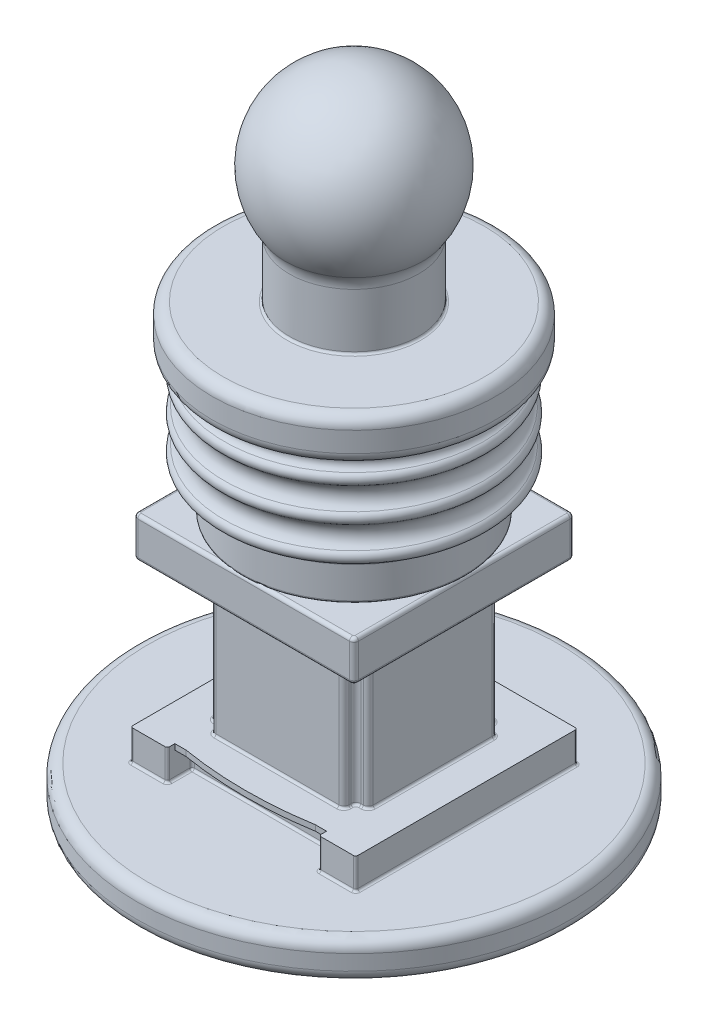
SolidWorks part; units mm, degrees
material "PE High Density"
ref_plane "Front Plane" through (0, 0, 0) normal (0, 0, 1) x (1, 0, 0)
ref_plane "Top Plane" through (0, 0, 0) normal (0, 1, 0) x (1, 0, 0)
ref_plane "Right Plane" through (0, 0, 0) normal (1, 0, 0) x (0, 0, -1)
sketch "Sketch1" plane through (0, 0, 0) normal (0, 1, 0) x (1, 0, 0)
  circle A0 centre (0, 0) radius 9.65
  dimension "D1" = 19.3
extrude "Boss-Extrude1" add sketch "Sketch1" along normal blind 1.68 contours A0
fillet "Fillet1" radius 0.5 2 edges at (0, 0, 9.65) (0, 1.68, 9.65)
sketch "Sketch2" plane through (0, 1.68, 0) normal (0, 1, 0) x (1, 0, 0)
  line L1 (-5, -4.925) -> (5, -4.925)
  line L2 (-5, -4.925) -> (-5, 4.925)
  line L3 (-5, 4.925) -> (5, 4.925)
  line L4 (5, -4.925) -> (5, 4.925)
  line L5 (-5, -4.925) -> (5, 4.925) construction
  line L6 (-5, 4.925) -> (5, -4.925) construction
  point P0 (0, 0)
  dimension "D1" = 10
  dimension "D2" = 9.85
extrude "Boss-Extrude2" add sketch "Sketch2" along normal offset from surface (1.37 mm away) 3.05 contours L3 L4 L1 L2 up to face at (0, 0, 9.15)
sketch "Sketch3" plane through (0, 0, 0) normal (0, -1, 0) x (1, 0, 0)
  circle A0 centre (0, 0) radius 2.885
  dimension "D1" = 5.77
extrude "Boss-Extrude3" add sketch "Sketch3" along normal blind 2.25 contours A0
sketch "Sketch4" plane through (0, 0, 4.925) normal (0, 0, 1) x (1, 0, 0)
  line L0 (9.15, 1.68) -> (-9.15, 1.68) construction
  line L1 (-3.37, 1.68) -> (3.37, 1.68)
  line L2 (-3.37, 1.68) -> (-3.37, 2.8)
  line L3 (-3.37, 2.8) -> (3.37, 2.8)
  line L4 (3.37, 1.68) -> (3.37, 2.8)
  line L5 (0, 0) -> (0, 2.8) construction
  line L6 (-5, 3.05) -> (-5, 1.68) construction
  line L7 (-5, 3.05) -> (5, 3.05) construction
  dimension "D1" = 1.63
  dimension "D2" = 0.25
extrude "Cut-Extrude1" cut sketch "Sketch4" against normal blind 1.1
sketch "Sketch5" plane through (0, 3.05, 0) normal (0, 1, 0) x (1, 0, 0)
  line L0 (-3.37, -4.925) -> (-3.37, -4.5881)
  line L1 (-5, -4.925) -> (5, -4.925) construction
  line L2 (3.37, -4.925) -> (3.37, -4.5881)
  line L3 (0, 0) -> (0, -4.925) construction
  line L4 (-3.37, -4.925) -> (3.37, -4.925)
  line L5 (-3.37, -4.5881) -> (-2.87, -4.5881)
  line L6 (3.37, -4.5881) -> (2.87, -4.5881)
  arc A0 (-2.87, -4.5881) -> (2.87, -4.5881) centre (0, 12.675) ccw
  point P12 (0, -4.825)
  dimension "D1" = 0.1
  dimension "D2" = 35
  dimension "D3" = 0.5
extrude "Cut-Extrude2" cut sketch "Sketch5" against normal up to next
sketch "Sketch7" plane through (0, 3.05, 0) normal (0, 1, 0) x (1, 0, 0)
  line L0 (-3.5, 0) -> (0, 0) construction
  line L1 (-3.5, -3.4) -> (3.5, -3.4)
  line L2 (-3.5, -3.4) -> (-3.5, 3.4)
  line L3 (-3.5, 3.4) -> (3.5, 3.4)
  line L4 (3.5, -3.4) -> (3.5, 3.4)
  line L5 (-3.5, -3.4) -> (3.5, 3.4) construction
  line L6 (-3.5, 3.4) -> (3.5, -3.4) construction
  line L7 (0, 0) -> (0, 3.4) construction
  line L8 (2.95, 3.4) -> (2.95, 2.8657)
  line L9 (-3.5, 3.4) -> (-2.95, 3.4)
  line L10 (-3.5, 3.4) -> (-3.5, 2.8657)
  line L11 (-3.5, 2.8657) -> (-2.95, 2.8657)
  line L12 (-2.95, 3.4) -> (-2.95, 2.8657)
  line L13 (3.5, 2.8657) -> (2.95, 2.8657)
  line L14 (3.5, -2.8657) -> (2.95, -2.8657)
  line L15 (2.95, -3.4) -> (2.95, -2.8657)
  line L16 (-3.5, -2.8657) -> (-2.95, -2.8657)
  line L17 (-2.95, -3.4) -> (-2.95, -2.8657)
  point P0 (0, 0)
  dimension "D1" = 7
  dimension "D2" = 6.8
  dimension "D3" = 5.9
extrude "Boss-Extrude4" add sketch "Sketch7" along normal blind 6.5 contours L17 L1 L15 L14 L4 L13 L8 L3 L12 L11 L2 L16 region at (0, 3.05, 0)
fillet "Fillet2" radius 0.22 12 edges at (3.5, 6.3, -2.8657) (2.95, 6.3, -2.8657) (2.95, 6.3, -3.4) (-2.95, 6.3, -3.4) (-2.95, 6.3, -2.8657) (-3.5, 6.3, -2.8657) (-2.95, 6.3, 3.4) (-2.95, 6.3, 2.8657) (-3.5, 6.3, 2.8657) (2.95, 6.3, 2.8657) (3.5, 6.3, 2.8657) (2.95, 6.3, 3.4)
fillet "Fillet3" radius 0.1 24 edges at (-2.8856, 3.05, 3.3356) (-2.95, 3.05, 3.1329) (-3.0144, 3.05, 2.9302) (-3.225, 3.05, 2.8657) (-3.4356, 3.05, 2.8013) (-3.5, 3.05, 0) (-3.4356, 3.05, -2.8013) (-3.225, 3.05, -2.8657) (-3.0144, 3.05, -2.9302) (-2.95, 3.05, -3.1329) (-2.8856, 3.05, -3.3356) (0, 3.05, -3.4) (2.8856, 3.05, -3.3356) (2.95, 3.05, -3.1329) (3.0144, 3.05, -2.9302) (3.225, 3.05, -2.8657) (3.4356, 3.05, -2.8013) (3.5, 3.05, 0) (3.4356, 3.05, 2.8013) (3.225, 3.05, 2.8657) (3.0144, 3.05, 2.9302) (2.95, 3.05, 3.1329) (2.8856, 3.05, 3.3356) (0, 3.05, 3.4)
fillet "Fillet4" radius 0.1 17 edges at (5, 1.68, 0) (5, 2.365, -4.925) (-5, 2.365, -4.925) (0, 0, 2.885) (-5, 2.365, 4.925) (5, 2.365, 4.925) (3.37, 2.365, 4.925) (3.37, 2.24, 3.825) (-3.37, 2.24, 3.825) (-3.37, 2.365, 4.925) (-5, 1.68, 0) (-4.185, 1.68, 4.925) (-3.37, 1.68, 4.375) (0, 1.68, 3.825) (3.37, 1.68, 4.375) (4.185, 1.68, 4.925) (0, 1.68, -4.925)
sketch "Sketch8" plane through (0, 9.55, 0) normal (0, 1, 0) x (1, 0, 0)
  line L1 (-4.9, -4.9) -> (4.9, -4.9)
  line L2 (-4.9, -4.9) -> (-4.9, 4.9)
  line L3 (-4.9, 4.9) -> (4.9, 4.9)
  line L4 (4.9, -4.9) -> (4.9, 4.9)
  line L5 (-4.9, -4.9) -> (4.9, 4.9) construction
  line L6 (-4.9, 4.9) -> (4.9, -4.9) construction
  point P0 (0, 0)
  dimension "D1" = 9.8
  dimension "D2" = 9.8
extrude "Boss-Extrude5" add sketch "Sketch8" along normal blind 1.78 contours L3 L4 L1 L2
fillet "Fillet5" radius 0.1 24 edges at (-2.8856, 9.55, 3.3356) (-2.95, 9.55, 3.1329) (-3.0144, 9.55, 2.9302) (-3.225, 9.55, 2.8657) (-3.4356, 9.55, 2.8013) (-3.5, 9.55, 0) (-3.4356, 9.55, -2.8013) (-3.225, 9.55, -2.8657) (-3.0144, 9.55, -2.9302) (-2.95, 9.55, -3.1329) (-2.8856, 9.55, -3.3356) (0, 9.55, -3.4) (2.8856, 9.55, -3.3356) (2.95, 9.55, -3.1329) (3.0144, 9.55, -2.9302) (3.225, 9.55, -2.8657) (3.4356, 9.55, -2.8013) (3.5, 9.55, 0) (3.4356, 9.55, 2.8013) (3.225, 9.55, 2.8657) (3.0144, 9.55, 2.9302) (2.95, 9.55, 3.1329) (2.8856, 9.55, 3.3356) (0, 9.55, 3.4)
fillet "Fillet6" radius 0.2 4 edges at (4.9, 10.44, -4.9) (4.9, 10.44, 4.9) (-4.9, 10.44, -4.9) (-4.9, 10.44, 4.9)
fillet "Fillet7" radius 0.15 16 edges at (-4.8414, 9.55, 4.8414) (-4.9, 9.55, 0) (-4.8414, 9.55, -4.8414) (0, 9.55, -4.9) (4.8414, 9.55, -4.8414) (4.9, 9.55, 0) (4.8414, 9.55, 4.8414) (-4.8414, 11.33, 4.8414) (-4.9, 11.33, 0) (-4.8414, 11.33, -4.8414) (0, 11.33, -4.9) (4.8414, 11.33, -4.8414) (4.9, 11.33, 0) (4.8414, 11.33, 4.8414) (0, 9.55, 4.9) (0, 11.33, 4.9)
sketch "Sketch9" plane through (0, 11.33, 0) normal (0, 1, 0) x (1, 0, 0)
  circle A0 centre (0, 0) radius 4.95
  dimension "D1" = 9.9
extrude "Boss-Extrude6" add sketch "Sketch9" along normal blind 1.5 separate body
fillet "Fillet11" radius 0.1 1 edges at (0, 11.33, 4.95)
combine bodies "Combine1" operation type add bodies to combine 108 107
hole_wizard "Ø1.6 (1.6) Diameter Hole2" positions "Sketch11" profile "Sketch10" hole size "Ø1.6" standard "ANSI Metric"
sketch "Sketch11" plane through (0, -2.25, 0) normal (0, -1, 0) x (-1, 0, 0)
  point P0 (0, 0)
sketch "Sketch10" plane through (0, -2.25, 0) normal (1, 0, 0) x (0, 0, -1)
  line L0 (0, 0) -> (0, 8.4807)
  line L1 (0, 8.4807) -> (0.8, 8)
  line L2 (0.8, 8) -> (0.8, 0)
  line L5 (0.8, 0) -> (0, 0)
  line L10 (0, 8.4807) -> (-0.8, 8) construction
  line L11 (0, -6.35) -> (0, 107.95) construction
  dimension "Hole Dia." = 1.6
  dimension "Hole Depth" = 8
  dimension "Drill Angle" = 118
ref_plane "Plane1" through (0, 19.45, 0) normal (0, -1, 0) x (-1, 0, 0)
sketch "Sketch12" plane through (0, 19.45, 0) normal (0, -1, 0) x (-1, 0, 0)
  circle A0 centre (0, 0) radius 6.3
  dimension "D1" = 12.6
extrude "Boss-Extrude7" add sketch "Sketch12" along normal blind 1.9 separate body contours A0
sketch "Sketch14" plane through (0, 0, 0) normal (0, 0, 1) x (1, 0, 0)
  line L0 (0, 19.45) -> (0, 28.45)
  line L1 (6.3, 19.45) -> (-6.3, 19.45) construction
  line L2 (-2.875, 22.2923) -> (-2.875, 19.45)
  line L3 (-2.875, 19.45) -> (0, 19.45)
  arc A0 (0, 28.45) -> (0, 20.95) centre (0, 24.7) ccw
  dimension "D1" = 7.5
  dimension "D2" = 9
  dimension "D3" = 2.875
revolve "Revolve1" add sketch "Sketch14" angle 360 about L0 region at (-1.5977, 20.4437, 0) region at (-1.5915, 24.7, 0)
fillet "Fillet8" radius 0.1 1 edges at (0, 19.45, -2.875)
fillet "Fillet9" radius 1 1 edges at (0, 22.2923, -2.875)
fillet "Fillet10" radius 0.5 2 edges at (0, 17.55, -6.3) (0, 19.45, -6.3)
sketch "Sketch15" plane through (0, 0, 0) normal (0, 0, 1) x (1, 0, 0)
  line L0 (0, 17.55) -> (0, 12.83)
  line L1 (-5.8, 17.55) -> (5.8, 17.55) construction
  line L2 (4.95, 12.83) -> (-4.95, 12.83) construction
  line L3 (0, 12.83) -> (-5.9, 12.83)
  line L4 (-5.9, 12.83) -> (-5.9, 17.55) construction
  line L5 (-5.9, 17.55) -> (0, 17.55)
  line L6 (-5.6, 17.55) -> (-5.6, 12.83) construction
  line L7 (-5.6, 13.69) -> (0, 13.69) construction
  line L8 (-5.6, 15.19) -> (0, 15.19) construction
  line L9 (-5.6, 16.69) -> (0, 16.69) construction
  line L10 (-4.95, 12.83) -> (-4.95, 11.43) construction
  line L11 (-5.5, 14.44) -> (0, 14.44) construction
  circle A0 centre (-5.6, 13.69) radius 0.3
  circle A1 centre (-5.6, 15.19) radius 0.3
  circle A2 centre (-5.6, 16.69) radius 0.3
  arc A3 (-5.7671, 16.4409) -> (-5.7671, 15.4391) centre (-6.1031, 15.94) cw
  arc A4 (-5.7671, 14.9409) -> (-5.7671, 13.9391) centre (-6.1031, 14.44) cw
  arc A5 (-5.5839, 13.3904) -> (-4.95, 12.83) centre (-5.5517, 12.7882) cw
  arc A6 (-5.7608, 16.9433) -> (-5.8, 17.55) centre (-5.9467, 17.2359) ccw
  arc A8 (-6.3, 18.05) -> (-5.8, 17.55) centre (-5.8, 18.05) ccw construction
  dimension "D1" = 0.6
  dimension "D2" = 5.9
  dimension "D3" = 1.5
  dimension "D4" = 5.5
revolve "Revolve2" add sketch "Sketch15" angle 360 about L0 region at (-2.7237, 15.2159, 0) region at (-5.6, 16.69, 0) region at (-5.6, 13.69, 0) region at (-5.6, 15.19, 0)
